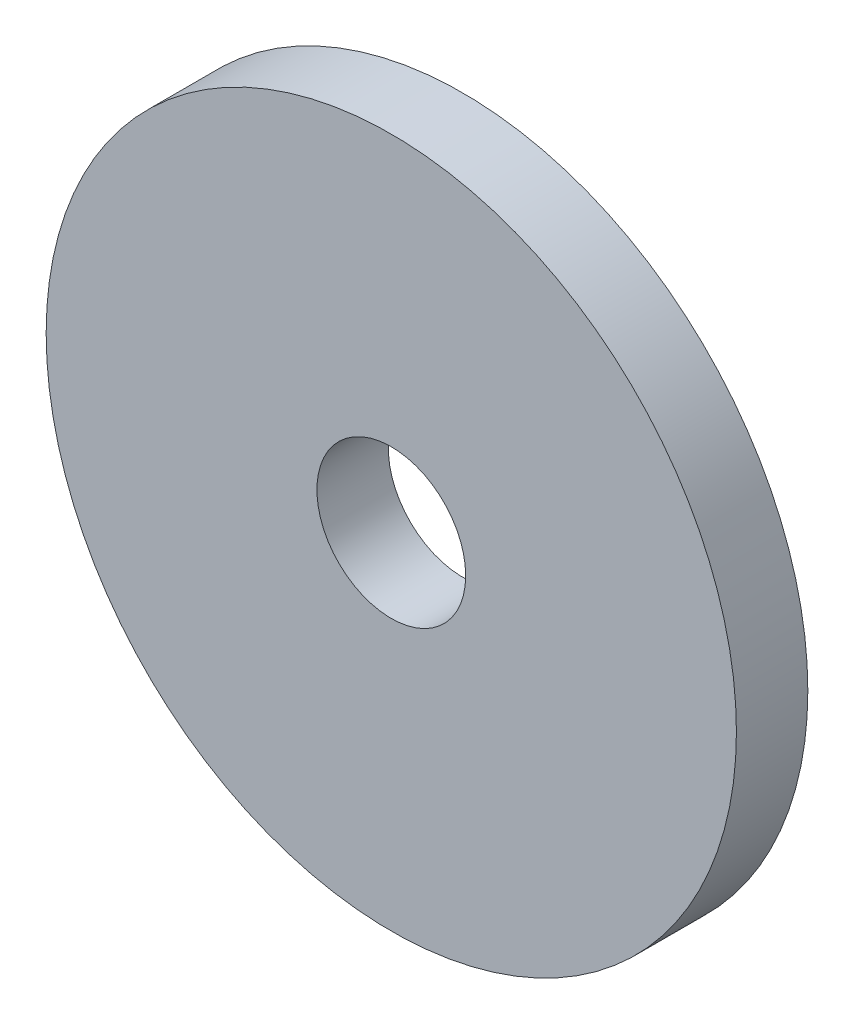
SolidWorks part; units mm, degrees
ref_plane "Front Plane" through (0, 0, 0) normal (0, 0, 1) x (1, 0, 0)
ref_plane "Top Plane" through (0, 0, 0) normal (0, 1, 0) x (1, 0, 0)
ref_plane "Right Plane" through (0, 0, 0) normal (1, 0, 0) x (0, 0, -1)
sketch "Sketch1" plane through (0, 0, 0) normal (0, 0, 1) x (1, 0, 0)
  circle A0 centre (0, 0) radius 14.732
  dimension "D1" = 29.464
extrude "Boss-Extrude1" add sketch "Sketch1" along normal blind 3.048 contours A0
sketch "Sketch2" plane through (0, 0, 3.048) normal (0, 0, 1) x (1, 0, 0)
  circle A0 centre (0, 0) radius 3.175
  dimension "D1" = 6.35
extrude "Cut-Extrude1" cut sketch "Sketch2" against normal blind 3.048
sketch "Sketch3" plane through (0, 0, 3.048) normal (0, 0, 1) x (1, 0, 0)
  circle A0 centre (29.464, 0) radius 14.732
  circle A1 centre (29.464, 43.561) radius 28.829
  dimension "D1" = 29.464
  dimension "D3" = 57.658
  dimension "D2" = 29.464
  dimension "D4" = 43.561
  dimension "D5" = 52.5898
